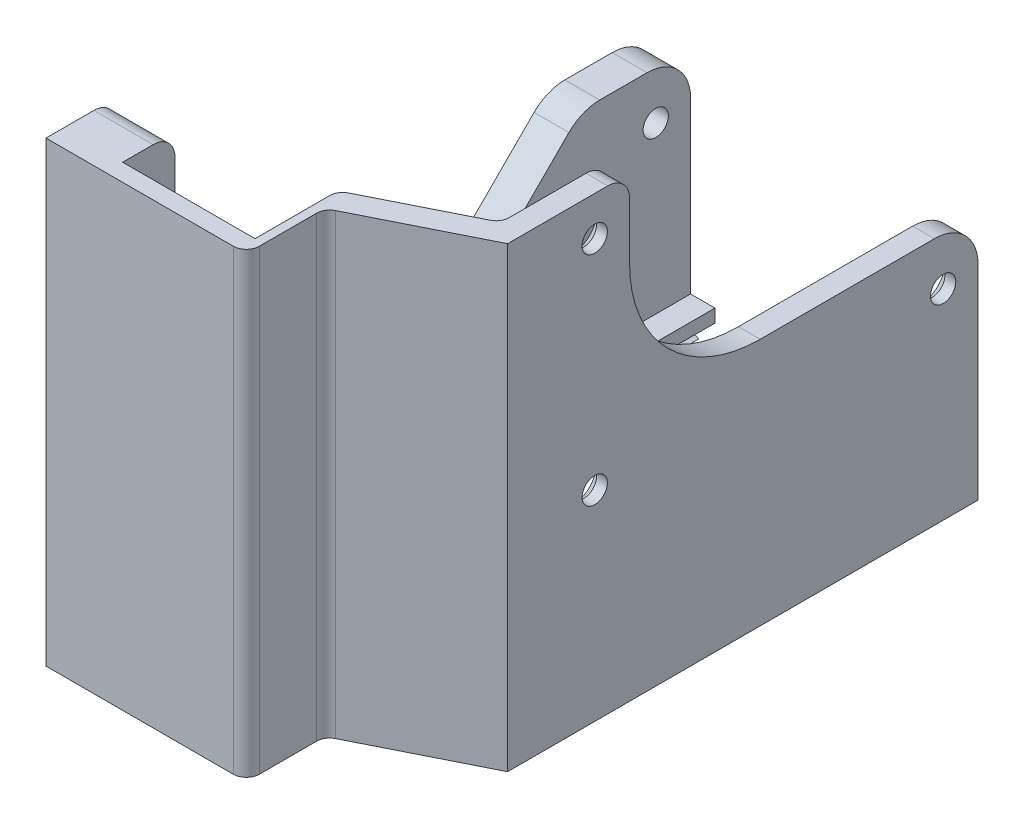
SolidWorks part; units mm, degrees
ref_plane "Спереди" through (0, 0, 0) normal (0, 0, 1) x (1, 0, 0)
ref_plane "Сверху" through (0, 0, 0) normal (0, 1, 0) x (1, 0, 0)
ref_plane "Справа" through (0, 0, 0) normal (1, 0, 0) x (0, 0, -1)
sketch "Эскиз2" plane through (0, 0, 0) normal (0, 1, 0) x (1, 0, 0)
  line L0 (0, -287.0595) -> (0, 0) construction
  line L1 (0, 0) -> (65.4832, 0) construction
  line L2 (52.3789, 0) -> (52.3789, -108)
  line L3 (52.3789, -108) -> (24.3789, -122)
  line L4 (24.3789, -122) -> (24.3789, -140)
  line L5 (24.3789, -140) -> (0, -140)
  line L8 (22.3789, 0) -> (22.3789, -136)
  line L9 (22.3789, -136) -> (0, -136)
  line L10 (0, -136) -> (-8.0211, -136)
  line L11 (-8.0211, -136) -> (-8.0211, 0)
  line L12 (-8.0211, 0) -> (-21.6211, 0)
  line L13 (-21.6211, 0) -> (-21.6211, -140)
  line L14 (-21.6211, -140) -> (0, -140)
  line L15 (22.3789, 0) -> (52.3789, 0)
  line L16 (-8.0211, -22.3266) -> (22.3789, -22.3266) construction
  line L17 (7.1789, -22.3266) -> (7.1789, 3.9751) construction
  dimension "D2" = 4
  dimension "D3" = 2
  dimension "D4" = 32
  dimension "D5" = 28
  dimension "D6" = 140
  dimension "D7" = 18
  dimension "D8" = 74
  dimension "D9" = 108
  dimension "D10" = 13.6
  dimension "D11" = 30.4
  dimension "D12" = 28.8
  dimension "D13" = 63.435
extrude "Бобышка-Вытянуть1" add sketch "Эскиз2" along normal blind 105
sketch "Эскиз4" plane through (0, 0, 0) normal (0, -1, 0) x (1, 0, 0)
  line L0 (-21.6211, 0) -> (52.3789, 0)
  line L1 (52.3789, 0) -> (52.3789, 108)
  line L2 (52.3789, 108) -> (24.3789, 122)
  line L3 (24.3789, 122) -> (24.3789, 140)
  line L4 (24.3789, 140) -> (-21.6211, 140)
  line L5 (-21.6211, 140) -> (-21.6211, 0)
sketch "Эскиз7" plane through (0, 0, 0) normal (0, -1, 0) x (1, 0, 0)
  line L0 (22.3789, 0) -> (22.3789, 136) construction
  line L1 (-8.0211, 136) -> (22.3789, 136)
  line L2 (-8.0211, 136) -> (-8.0211, 117)
  line L3 (-8.0211, 117) -> (22.3789, 117)
  line L4 (22.3789, 136) -> (22.3789, 117)
  dimension "D1" = 19
extrude "Бобышка-Вытянуть2" add sketch "Эскиз7" against normal blind 3 separate body
sketch "Эскиз8" plane through (0, 3, 0) normal (0, 1, 0) x (1, 0, 0)
  line L0 (-8.0211, -136) -> (-8.0211, -117) construction
  line L1 (22.3789, -136) -> (-8.0211, -136)
  line L2 (22.3789, -136) -> (22.3789, -124)
  line L3 (22.3789, -124) -> (-8.0211, -124)
  line L4 (-8.0211, -136) -> (-8.0211, -124)
  dimension "D1" = 12
extrude "Бобышка-Вытянуть3" add sketch "Эскиз8" along normal blind 38
fillet "Скругление1" radius 5 1 edges at (7.1789, 41, 124)
sketch "Эскиз3" plane through (0, 0, 0) normal (0, 0, -1) x (-1, 0, 0)
  line L0 (8.0211, -1.66) -> (19.3211, 3.4)
  line L1 (19.3211, 3.4) -> (19.3211, 5)
  line L2 (19.3211, 5) -> (8.0211, 5)
  line L3 (8.0211, 105) -> (8.0211, 0) construction
  line L4 (8.0211, 5) -> (8.0211, -1.66)
  line L5 (-7.1789, 0) -> (-7.1789, 26.9133) construction
  line L6 (-22.3789, 0) -> (8.0211, 0) construction
  line L7 (-33.6789, 5) -> (-22.3789, 5)
  line L8 (-33.6789, 3.4) -> (-33.6789, 5)
  line L9 (-22.3789, -1.66) -> (-33.6789, 3.4)
  line L10 (-22.3789, 5) -> (-22.3789, -1.66)
  line L11 (-24.3789, 0) -> (21.6211, 0) construction
  line L13 (-27.1789, 0) -> (12.8211, 0) construction
  line L14 (-27.1789, 0) -> (-27.1789, 5) construction
  line L15 (-27.1789, 5) -> (12.8211, 5) construction
  line L16 (12.8211, 0) -> (12.8211, 5) construction
  line L17 (-7.1789, 5) -> (-7.1789, 0) construction
  line L18 (-27.1789, 2.5) -> (12.8211, 2.5) construction
  point P2 (-7.1789, 2.5)
  point P20 (0, 0)
  dimension "D1" = 6.66
  dimension "D2" = 1.6
  dimension "D3" = 5
  dimension "D4" = 53
  dimension "D5" = 15.2
  dimension "D6" = 15.2
  dimension "D7" = 11.3
  dimension "D8" = 40
  dimension "D9" = 5
extrude "Вырез-Вытянуть1" cut sketch "Эскиз3" against normal up to surface (117 mm away) up to face at (7.1789, 1.5, 117)
sketch "Эскиз9" plane through (0, 105, 0) normal (0, 1, 0) x (1, 0, 0)
  line L0 (-21.6211, 0) -> (-21.6211, -96)
  line L1 (-21.6211, 0) -> (52.3789, 0) construction
  line L2 (-21.6211, -96) -> (22.3789, -96)
  line L3 (22.3789, 0) -> (22.3789, -136) construction
  line L4 (22.3789, -124) -> (22.3789, -129) construction
  line L5 (22.3789, -96) -> (22.3789, -117)
  line L6 (-8.0211, -117) -> (22.3789, -117) construction
  line L7 (22.3789, -117) -> (47.3789, -104.5)
  line L8 (47.3789, -104.5) -> (47.3789, 0)
  line L9 (47.3789, 0) -> (-21.6211, 0)
  line L10 (22.3789, -136) -> (-8.0211, -136) construction
  line L13 (52.3789, 0) -> (52.3789, -108) construction
  line L14 (52.3789, -108) -> (24.3789, -122) construction
  dimension "D1" = 40
  dimension "D2" = 5.3666
  dimension "D3" = 5
extrude "Вырез-Вытянуть2" cut sketch "Эскиз9" against normal offset from surface (97 mm away) 3 up to face at (28.0289, 5, 58.5)
sketch "Эскиз11" plane through (-21.6211, 0, 0) normal (-1, 0, 0) x (0, 0, 1)
  line L0 (103.6, 88.4738) -> (103.6, 19.9227) construction
  line L1 (122, 0) -> (140, 0) construction
  line L2 (140, 105) -> (140, 0) construction
  circle A0 centre (103.6, 41.2) radius 5
  dimension "D2" = 10
  dimension "D3" = 41.2
  dimension "D4" = 36.4
extrude "Вырез-Вытянуть4" cut sketch "Эскиз11" against normal blind 6.8 and the other way through all
fillet "Скругление3" radius 3 4 edges at (47.3789, 56.5, 104.5) (24.3789, 52.5, 122) (24.3789, 52.5, 140) (22.3789, 56.5, 117)
sketch "Эскиз12" plane through (-21.6211, 0, 0) normal (-1, 0, 0) x (0, 0, 1)
  circle A0 centre (103.6, 41.2) radius 2.6
  dimension "D1" = 5.2
extrude "Вырез-Вытянуть5" cut sketch "Эскиз12" against normal blind 20
chamfer "Фаска1" distance 3 angle 45 1 edges at (-14.8211, 41.2, 106.2)
sketch "Эскиз13" plane through (-21.6211, 0, 0) normal (-1, 0, 0) x (0, 0, 1)
  line L0 (140, 105) -> (140, 0) construction
  line L1 (33.0864, 46) -> (88, 46) construction
  line L2 (88, 46) -> (88, 141.3627) construction
  line L3 (0, 0) -> (108, 0) construction
  circle A0 centre (88, 46) radius 2.9
  circle A1 centre (8, 46) radius 2.9
  circle A3 centre (88, 96) radius 2.9
  dimension "D1" = 5.8
  dimension "D2" = 50
  dimension "D3" = 80
  dimension "D4" = 52
  dimension "D5" = 46
  dimension "D6" = 20
extrude "Вырез-Вытянуть6" cut sketch "Эскиз13" against normal through all
chamfer "Фаска3" distance 2.5 angle 45 3 edges at (47.3789, 46, 5.1) (47.3789, 46, 85.1) (47.3789, 96, 85.1)
sketch "Эскиз16" plane through (-21.6211, 0, 0) normal (-1, 0, 0) x (0, 0, 1)
  line L0 (80, 105) -> (80, 57)
  line L1 (96, 105) -> (140, 105) construction
  line L2 (80, 57) -> (0, 57)
  line L3 (0, 8) -> (0, 0) construction
  line L4 (0, 57) -> (0, 105)
  line L5 (0, 105) -> (80, 105)
  line L6 (140, 105) -> (140, 0) construction
  dimension "D1" = 60
  dimension "D2" = 48
extrude "Вырез-Вытянуть9" cut sketch "Эскиз16" against normal through all
fillet "Скругление4" radius 30 1 edges at (49.8789, 57, 80)
sketch "Эскиз17" plane through (-21.6211, 0, 0) normal (-1, 0, 0) x (0, 0, 1)
  line L0 (96, 105) -> (140, 105) construction
  line L1 (124, 105) -> (96, 105)
  line L2 (124, 105) -> (124, 53)
  line L3 (124, 53) -> (96, 53)
  line L4 (96, 105) -> (96, 53)
  line L5 (96, 8) -> (96, 105) construction
  line L6 (140, 105) -> (140, 0) construction
  dimension "D1" = 16
  dimension "D2" = 52
extrude "Вырез-Вытянуть10" cut sketch "Эскиз17" against normal blind 20
fillet "Скругление5" radius 8 2 edges at (-14.8211, 53, 124) (-14.8211, 53, 96)
sketch "Эскиз18" plane through (0, 8, 0) normal (0, 1, 0) x (1, 0, 0)
  line L0 (-21.6211, -140) -> (-21.6211, 0) construction
  line L1 (-13.6211, -24) -> (-21.6211, -24)
  line L2 (-13.6211, -24) -> (-13.6211, 0)
  line L3 (-13.6211, 0) -> (-21.6211, 0)
  line L4 (-21.6211, -24) -> (-21.6211, 0)
  line L5 (24.3789, -140) -> (-21.6211, -140) construction
  dimension "D1" = 8
  dimension "D3" = 116
extrude "Бобышка-Вытянуть4" add sketch "Эскиз18" along normal up to surface (49 mm away) up to face at (49.8789, 57, 25)
chamfer "Фаска4" distance 50 angle 45 1 edges at (-17.6211, 8, 24)
fillet "Скругление6" radius 10 2 edges at (49.8789, 57, 0) (-17.6211, 57, 0)
sketch "Эскиз19" plane through (52.3789, 0, 0) normal (1, 0, 0) x (0, 0, -1)
  circle A0 centre (-8, 46) radius 2.9
extrude "Вырез-Вытянуть11" cut sketch "Эскиз19" against normal through all
chamfer "Фаска5" distance 2.6 angle 45 1 edges at (-21.6211, 46, 5.1)
sketch "Эскиз21" plane through (-21.6211, 0, 0) normal (-1, 0, 0) x (0, 0, 1)
  line L0 (130, 108.683) -> (130, -7.686) construction
  line L1 (140, 105) -> (140, 0) construction
  line L2 (122, 0) -> (140, 0) construction
  circle A0 centre (130, 30) radius 2.3
  circle A1 centre (130, 90) radius 2.3
  dimension "D2" = 4.6
  dimension "D3" = 60
  dimension "D1" = 10
  dimension "D4" = 30
extrude "Вырез-Вытянуть13" cut sketch "Эскиз21" against normal blind 15
fillet "Скругление7" radius 5 2 edges at (-14.8211, 105, 124) (49.8789, 105, 80)
chamfer "Фаска6" distance 0.8 angle 45 3 edges at (-21.6211, 41.2, 98.6) (-21.6211, 30, 132.3) (-21.6211, 90, 132.3)
sketch "Эскиз22" plane through (0, 8, 0) normal (0, 1, 0) x (1, 0, 0)
  line L0 (-13.6211, -25) -> (-13.6211, -74) construction
  line L1 (-21.6211, -96) -> (-13.6211, -96)
  line L2 (-21.6211, -96) -> (-21.6211, -47.3162)
  line L3 (-21.6211, -47.3162) -> (-13.6211, -47.3162)
  line L4 (-13.6211, -96) -> (-13.6211, -47.3162)
  line L5 (-13.6211, -74) -> (-13.6211, 0) construction
extrude "Бобышка-Вытянуть5" add sketch "Эскиз22" along normal blind 10
fillet "Скругление8" radius 10 1 edges at (-17.6211, 57, 25)
